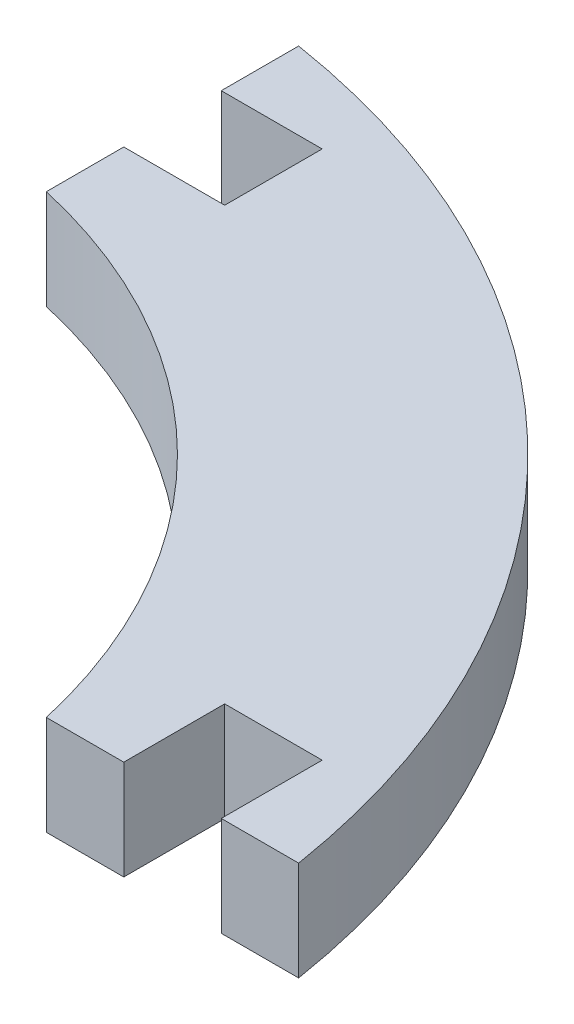
SolidWorks part; units mm, degrees
ref_plane "Front Plane" through (0, 0, 0) normal (0, 0, 1) x (1, 0, 0)
ref_plane "Top Plane" through (0, 0, 0) normal (0, 1, 0) x (1, 0, 0)
ref_plane "Right Plane" through (0, 0, 0) normal (1, 0, 0) x (0, 0, -1)
sketch "Sketch1" plane through (0, 0, 0) normal (0, 1, 0) x (1, 0, 0)
  line L0 (-14.362, 0) -> (33.8292, 0) construction
  line L1 (-14.362, 0) -> (-14.362, 39.7265) construction
  line L2 (19.1615, 0) -> (14.291, 0)
  line L3 (-14.362, 33.5235) -> (-14.362, 28.6531)
  line L4 (-17.537, 36.5906) -> (-8.012, 36.5906) construction
  line L5 (-8.012, 33.5235) -> (-8.012, 39.6576)
  line L6 (-8.012, 39.6576) -> (-14.362, 39.6576)
  line L7 (-8.012, 33.5235) -> (-14.362, 33.5235)
  line L9 (22.2285, 1.9269) -> (22.2285, 9.6366) construction
  line L10 (19.1615, 0) -> (19.1615, 6.35)
  line L11 (19.1615, 6.35) -> (25.2956, 6.35)
  line L12 (25.2956, 0) -> (25.2956, 6.35)
  line L14 (-14.362, 44.5281) -> (-14.362, 39.6576)
  line L15 (30.166, 0) -> (25.2956, 0)
  arc A0 (-14.362, 44.5281) -> (30.166, 0) centre (-22.8512, -8.4892) cw
  arc A1 (-14.362, 28.6531) -> (14.291, 0) centre (-22.8512, -8.4892) cw
  point P22 (22.2285, 6.35)
  dimension "D3" = 38.1
  dimension "D1" = 15.875
  dimension "D2" = 7.9375
  dimension "slot_depth" = 6.35
  dimension "press_fit_width" = 6.1341
extrude "Boss-Extrude1" add sketch "Sketch1" along normal blind 6.2611
equation "\"slot_width\"=0.2465"
equation "\"slot_depth\"= 0.25    "
equation "\"half_slot_width\"= \"slot_width\" /2"
equation "\"D2@Sketch1\" = \"D1@Sketch1\"/2"
equation "\"press_fit_width\"= \"slot_width\"-0.005"
